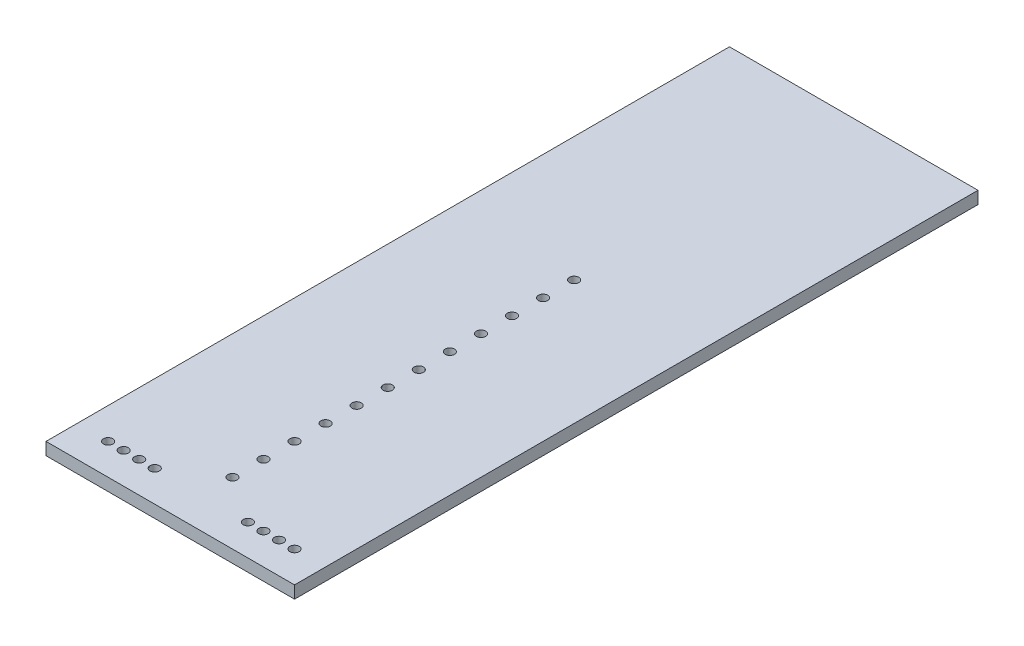
SolidWorks part; units mm, degrees
ref_plane "Front Plane" through (0, 0, 0) normal (0, 0, 1) x (1, 0, 0)
ref_plane "Top Plane" through (0, 0, 0) normal (0, 1, 0) x (1, 0, 0)
ref_plane "Right Plane" through (0, 0, 0) normal (1, 0, 0) x (0, 0, -1)
sketch "Sketch2" plane through (0, 0, 0) normal (0, 1, 0) x (1, 0, 0)
  line L1 (-40, -110) -> (40, -110)
  line L2 (-40, -110) -> (-40, 110)
  line L3 (-40, 110) -> (40, 110)
  line L4 (40, -110) -> (40, 110)
  line L5 (-40, -110) -> (40, 110) construction
  line L6 (-40, 110) -> (40, -110) construction
  point P0 (0, 0)
  dimension "D1" = 80
  dimension "D2" = 220
extrude "main_plate" add sketch "Sketch2" along normal blind 4
sketch "Sketch3" plane through (0, 4, 0) normal (0, 1, 0) x (1, 0, 0)
  line L0 (0, 124.2125) -> (0, -124.2125) construction
  line L1 (-40, -110) -> (40, -110) construction
  circle A0 centre (30, -100) radius 1.5
  circle A3 centre (25, -100) radius 1.5
  circle A4 centre (20, -100) radius 1.5
  circle A5 centre (15, -100) radius 1.5
  point P4 (0, 0)
  dimension "D1" = 3
  dimension "D3" = 4
  dimension "D2" = 30
  dimension "D7" = 10
extrude "elbow_holes" cut sketch "Sketch3" against normal through all
sketch "Sketch4" plane through (0, 4, 0) normal (0, 1, 0) x (1, 0, 0)
  line L0 (-40, -110) -> (40, -110) construction
  circle A0 centre (0, -90) radius 1.5
  circle A1 centre (0, -80) radius 1.5
  circle A2 centre (0, -70) radius 1.5
  circle A3 centre (0, -60) radius 1.5
  circle A4 centre (0, -50) radius 1.5
  circle A5 centre (0, -40) radius 1.5
  circle A6 centre (0, -30) radius 1.5
  circle A7 centre (0, -20) radius 1.5
  circle A8 centre (0, -10) radius 1.5
  circle A9 centre (0, 0) radius 1.5
  circle A10 centre (0, 10) radius 1.5
  circle A11 centre (0, 20) radius 1.5
  point P4 (0, 0)
  point P7 (0, -110)
  dimension "D1" = 3
  dimension "D2" = 0
  dimension "D4" = 20
  dimension "D3" = 12
extrude "pin_holes" cut sketch "Sketch4" against normal through all
mirror "Mirror1" about plane through (0, 0, 0) normal (1, 0, 0) of "elbow_holes"
